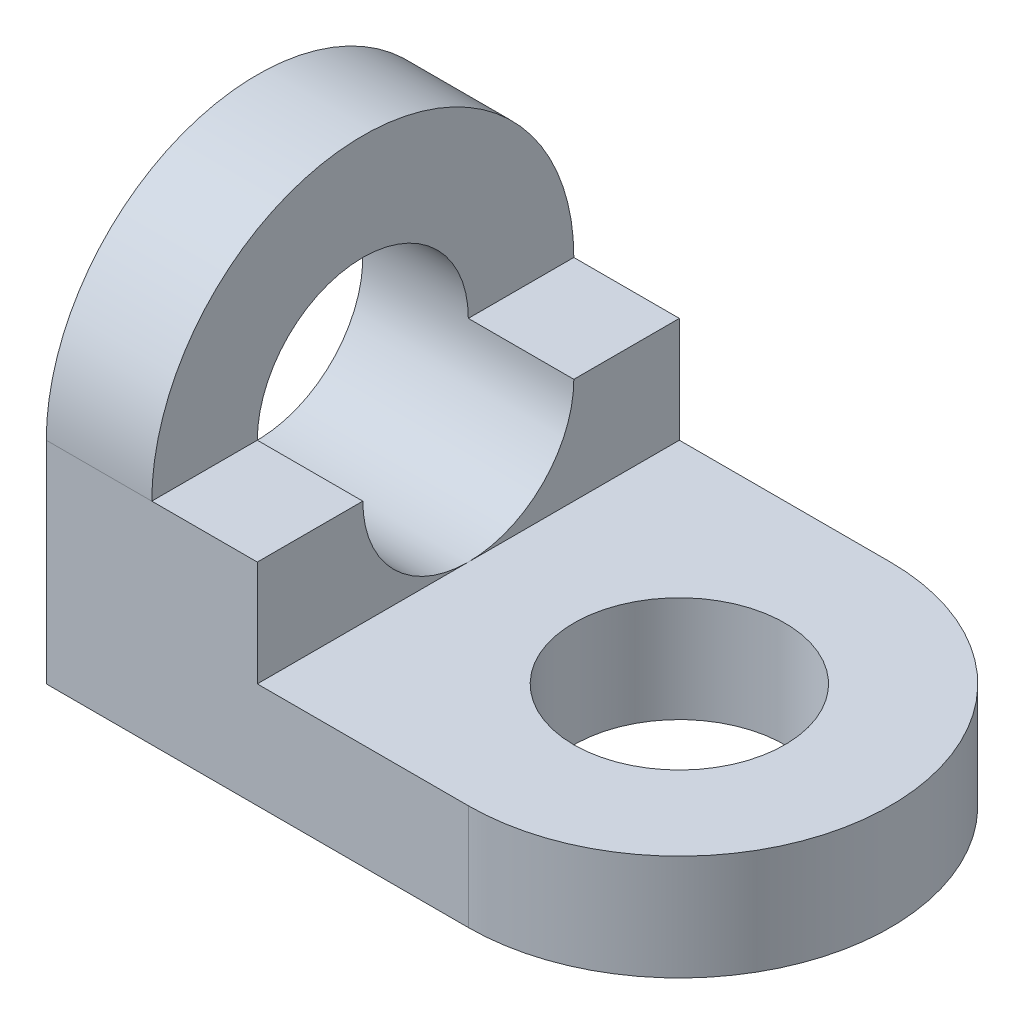
SolidWorks part; units mm, degrees
ref_plane "Front Plane" through (0, 0, 0) normal (0, 0, 1) x (1, 0, 0)
ref_plane "Top Plane" through (0, 0, 0) normal (0, 1, 0) x (1, 0, 0)
ref_plane "Right Plane" through (0, 0, 0) normal (1, 0, 0) x (0, 0, -1)
sketch "Sketch1" plane through (0, 0, 0) normal (0, 1, 0) x (1, 0, 0)
  line L0 (0, 0) -> (0, 1016)
  line L1 (0, 1016) -> (1016, 1016)
  line L2 (0, 508) -> (1524, 508) construction
  line L3 (1016, 0) -> (0, 0)
  line L4 (254, 1016) -> (254, 0)
  line L5 (508, 1016) -> (508, 0)
  arc A0 (1016, 0) -> (1016, 1016) centre (1016, 508) ccw
  circle A1 centre (1016, 508) radius 254
  dimension "D5" = 508
  dimension "D1" = 1016
  dimension "D2" = 1016
  dimension "D3" = 254
  dimension "D4" = 254
extrude "Boss-Extrude1" add sketch "Sketch1" along normal blind 254 contours L2 L5 L3 A0 A1 | L5 L2 A1 A0 L1 region at (955.2068, 0, -234.4305) region at (955.2068, 0, -781.5695)
extrude "Boss-Extrude2" add sketch "Sketch1<3>" along normal blind 508 contours L2 L4 L3 L5 | L4 L2 L5 L1 region at (381, 0, -254) region at (381, 0, -762)
sketch "Sketch1<3>" plane through (0, 0, 0) normal (0, 1, 0) x (1, 0, 0) same geometry as "Sketch1"
extrude "Boss-Extrude3" add sketch "Sketch1<4>" along normal blind 1016 contours L2 L0 L3 L4 | L0 L2 L4 L1 region at (127, 0, -254) region at (127, 0, -762)
sketch "Sketch1<4>" plane through (0, 0, 0) normal (0, 1, 0) x (1, 0, 0) same geometry as "Sketch1"
sketch "Sketch2" plane through (0, 0, 0) normal (-1, 0, 0) x (0, 0, 1)
  line L1 (-1016, 1016) -> (-1016, 0) construction
  line L2 (0, 1016) -> (-1016, 1016) construction
  line L3 (0, 1016) -> (0, 0) construction
  line L4 (0, 508) -> (-1016, 508) construction
  line L5 (0, 508) -> (0, 1016)
  line L6 (0, 1016) -> (-1016, 1016)
  line L7 (-1016, 1016) -> (-1016, 508)
  arc A0 (0, 508) -> (-1016, 508) centre (-508, 508) ccw
  circle A1 centre (-508, 508) radius 254
  line M2 (0, 0) -> (0, 1016)
  line M3 (0, 1016) -> (-1016, 1016)
  line M4 (-1016, 1016) -> (-1016, 0)
  dimension "D1" = 508
extrude "Cut-Extrude2" cut sketch "Sketch2" against normal through all contours L4 A1 | A1 L4 region at (0, 400.1991, -508) region at (0, 615.8009, -508)
extrude "Cut-Extrude3" cut sketch "Sketch2<4>" against normal blind 254 contours A0 M2 M3 | A0 L6 M4 region at (0, 902.5291, -113.4709) region at (0, 902.5291, -902.5291)
sketch "Sketch2<4>" plane through (0, 0, 0) normal (-1, 0, 0) x (0, 0, 1) same geometry as "Sketch2"
